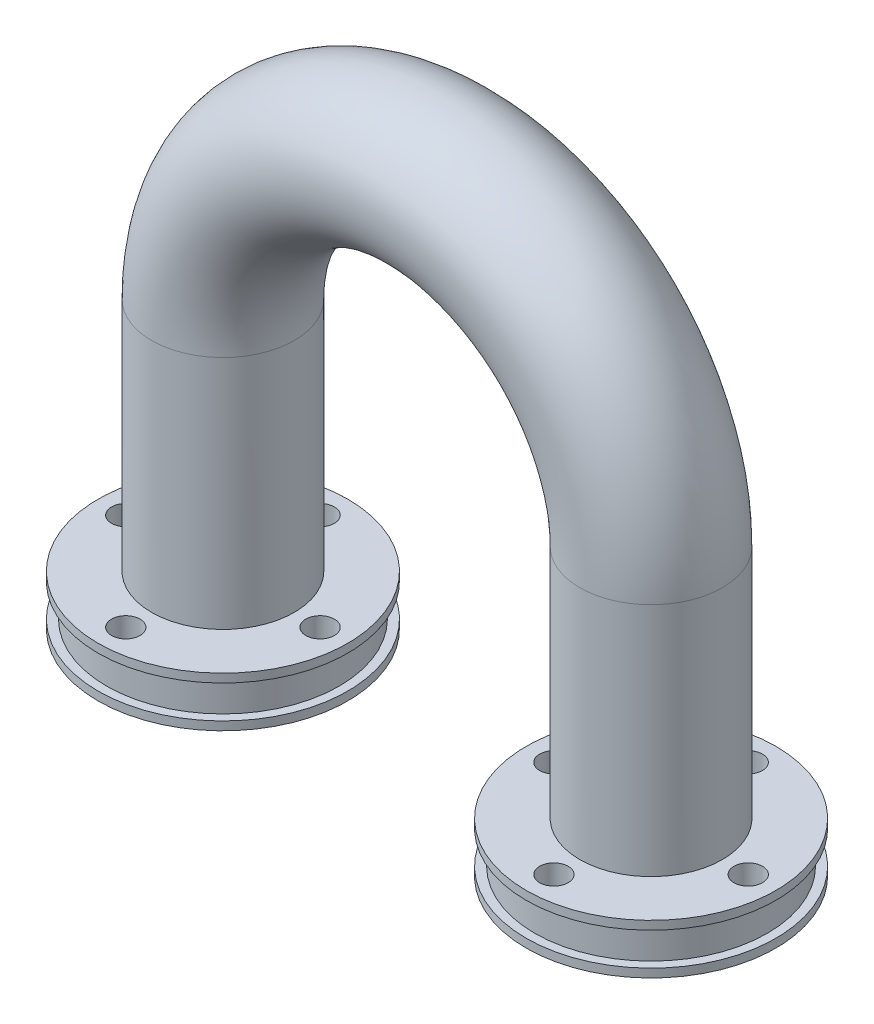
SolidWorks part; units mm, degrees
ref_plane "Front Plane" through (0, 0, 0) normal (0, 0, 1) x (1, 0, 0)
ref_plane "Top Plane" through (0, 0, 0) normal (0, 1, 0) x (1, 0, 0)
ref_plane "Right Plane" through (0, 0, 0) normal (1, 0, 0) x (0, 0, -1)
sketch "Sketch1" plane through (0, 0, 0) normal (0, 0, 1) x (1, 0, 0)
  line L0 (-30, 0) -> (-30, -33)
  line L1 (30, 0) -> (30, -33)
  arc A0 (30, 0) -> (-30, 0) centre (0, 0) ccw
  dimension "D1" = 60
  dimension "D2" = 33
  dimension "D3" = 60
ref_plane "Plane1" through (0, -33, 0) normal (0, 1, 0) x (1, 0, 0)
sketch "Sketch3" plane through (0, -33, 0) normal (0, 1, 0) x (1, 0, 0)
  circle A0 centre (-30, 0) radius 10
  dimension "D1" = 20
sweep "Sweep-Thin2" add profiles "Sketch3" path "Sketch1" parameters "D1"=4
sketch "Sketch4" plane through (0, 0, 0) normal (0, 0, 1) x (1, 0, 0)
  line L1 (36, -33) -> (47.5, -33)
  line L2 (36, -33) -> (36, -40)
  line L3 (11, -33) -> (-11, -33) construction
  line L4 (47.5, -33) -> (47.5, -34.2)
  line L5 (47.5, -34.2) -> (46.3, -34.2)
  line L6 (46.3, -34.2) -> (46.3, -38.8)
  line L7 (46.3, -38.8) -> (47.5, -38.8)
  line L8 (47.5, -38.8) -> (47.5, -40)
  line L9 (47.5, -40) -> (36, -40)
  line L10 (40, -33) -> (40, 0) construction
  line L11 (30, -33) -> (30, -40) construction
  point P6 (40, -33)
  point P13 (0, 0)
  dimension "D1" = 1.2
  dimension "D2" = 1.2
  dimension "D3" = 4.6
  dimension "D4" = 4
  dimension "D5" = 1.2
  dimension "D6" = 1.2
  dimension "D7" = 7.5
  dimension "D8" = 6
revolve "Revolve2" add sketch "Sketch4" angle 360 about L11
sketch "Sketch7" plane through (0, -33, 0) normal (0, 1, 0) x (1, 0, 0)
  line L0 (30, 0) -> (55.8213, 0) construction
  circle A0 centre (30, 0) radius 13.6148 construction
  circle A1 centre (43.6148, 0) radius 2
  dimension "D1" = 4
  dimension "26" = 27.2295
extrude "Cut-Extrude1" cut sketch "Sketch7" against normal through all
pattern_circular "CirPattern1" count 4 every 90 about axis through (30, 0, 0) along (0, -1, 0) of "Cut-Extrude1"
mirror "Mirror2" about plane through (0, 0, 0) normal (1, 0, 0) of "CirPattern1", "Revolve2"
